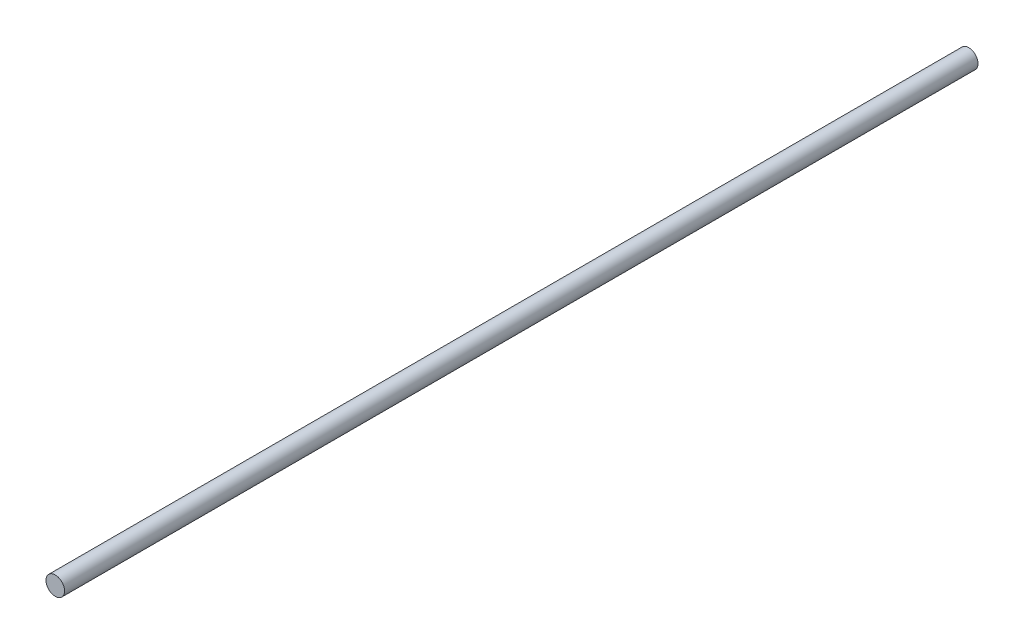
SolidWorks part; units mm, degrees
material "Plain Carbon Steel"
ref_plane "Спереди" through (0, 0, 0) normal (0, 0, 1) x (1, 0, 0)
ref_plane "Сверху" through (0, 0, 0) normal (0, 1, 0) x (1, 0, 0)
ref_plane "Справа" through (0, 0, 0) normal (1, 0, 0) x (0, 0, -1)
sketch "Sketch1" plane through (0, 0, 0) normal (0, 0, 1) x (1, 0, 0)
  circle A0 centre (0, 0) radius 3
  dimension "D1" = 6
extrude "Boss-Extrude1" add sketch "Sketch1" along normal blind 295
